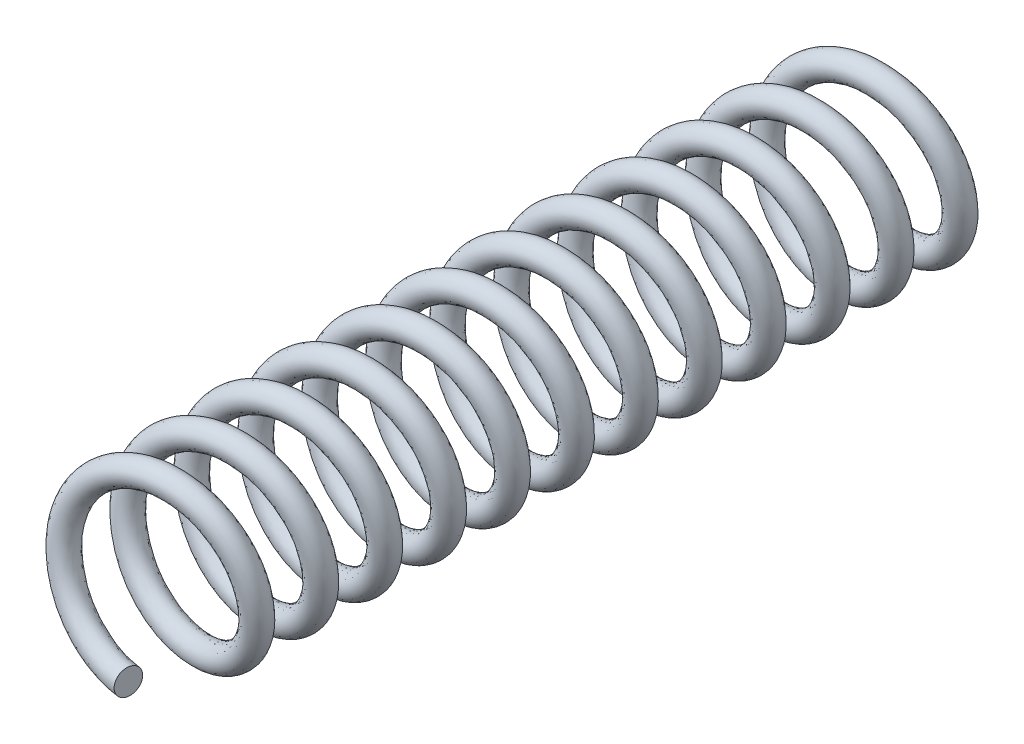
SolidWorks part; units mm, degrees
ref_plane "Front Plane" through (0, 0, 0) normal (0, 0, 1) x (1, 0, 0)
ref_plane "Top Plane" through (0, 0, 0) normal (0, 1, 0) x (1, 0, 0)
ref_plane "Right Plane" through (0, 0, 0) normal (1, 0, 0) x (0, 0, -1)
other "Configuration Table"
sketch "Sketch1" plane through (0, 0, 0) normal (0, 0, 1) x (1, 0, 0)
  circle A0 centre (0, 0) radius 3.175
  dimension "D1" = 6.35
curve "Helix/Spiral1" pitch 2.54 height 30.48 turns 12
sweep "Sweep1" add path "Helix/Spiral1" circular profile diameter 1.016 parameters "D3"=1.016
